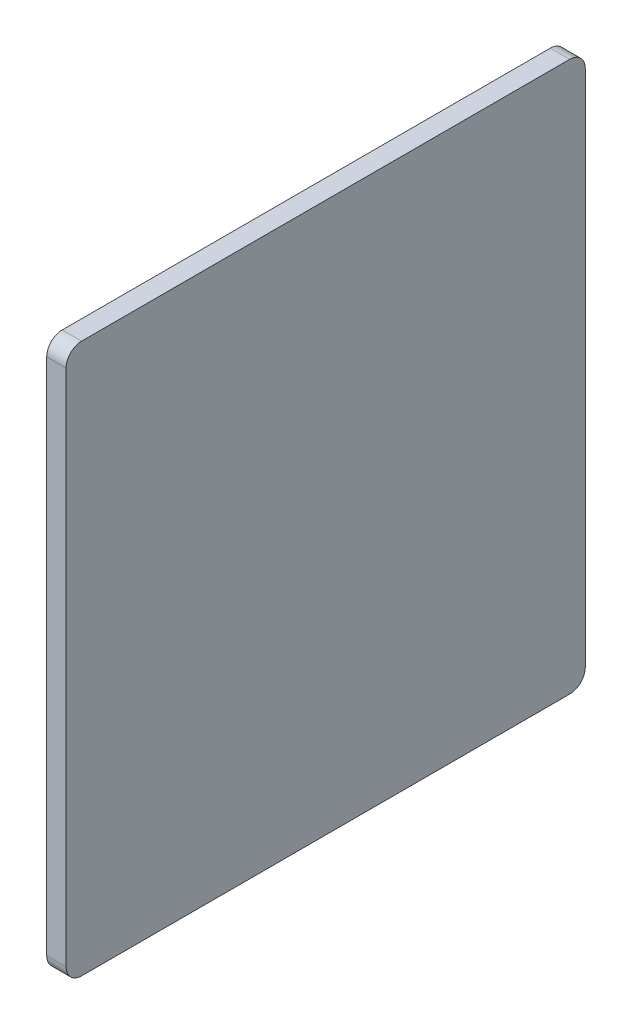
SolidWorks part; units mm, degrees
material "Acrylic (Medium-high impact)"
ref_plane "Front Plane" through (0, 0, 0) normal (0, 0, 1) x (1, 0, 0)
ref_plane "Top Plane" through (0, 0, 0) normal (0, 1, 0) x (1, 0, 0)
ref_plane "Right Plane" through (0, 0, 0) normal (1, 0, 0) x (0, 0, -1)
sketch "Sketch1" plane through (0, 0, 0) normal (1, 0, 0) x (0, 0, -1)
  line L1 (42.5, -45) -> (-42.5, -45)
  line L2 (42.5, -45) -> (42.5, 45)
  line L3 (42.5, 45) -> (-42.5, 45)
  line L4 (-42.5, -45) -> (-42.5, 45)
  line L5 (42.5, -45) -> (-42.5, 45) construction
  line L6 (42.5, 45) -> (-42.5, -45) construction
  point P0 (0, 0)
  dimension "D1" = 85
  dimension "D2" = 90
extrude "Boss-Extrude1" add sketch "Sketch1" along normal blind 3.175
fillet "Fillet1" radius 2.54 4 edges at (1.5875, -45, 42.5) (1.5875, -45, -42.5) (1.5875, 45, -42.5) (1.5875, 45, 42.5)
